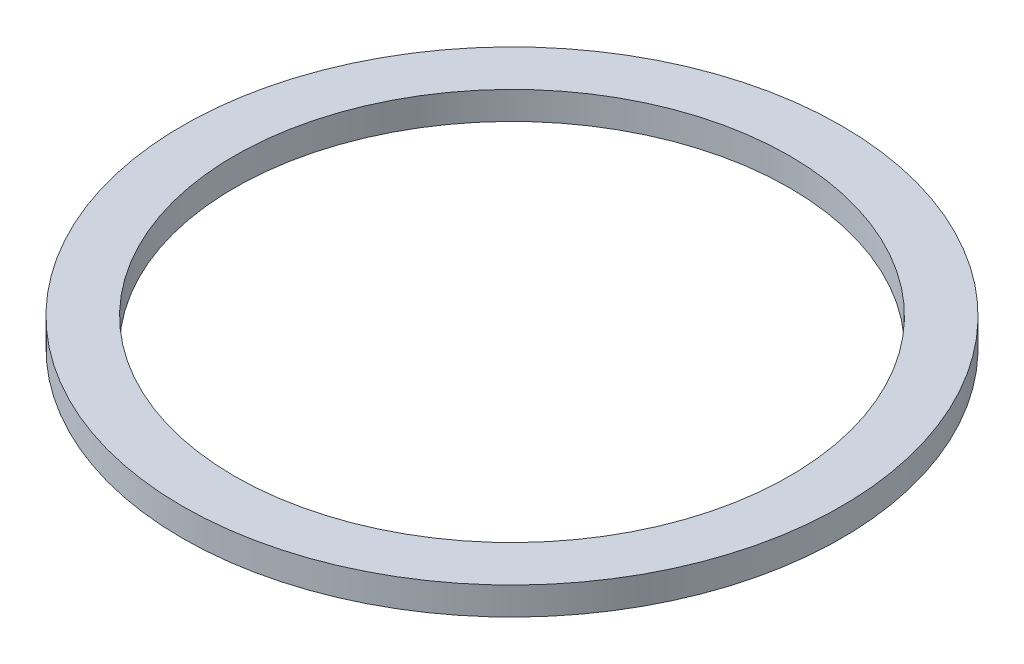
SolidWorks part; units mm, degrees
ref_plane "Front Plane" through (0, 0, 0) normal (0, 0, 1) x (1, 0, 0)
ref_plane "Top Plane" through (0, 0, 0) normal (0, 1, 0) x (1, 0, 0)
ref_plane "Right Plane" through (0, 0, 0) normal (1, 0, 0) x (0, 0, -1)
sketch "Sketch1" plane through (0, 0, 0) normal (0, 1, 0) x (1, 0, 0)
  circle A0 centre (0, 0) radius 47.5
  dimension "FLANGE_OD" = 95
extrude "Boss-Extrude1" add sketch "Sketch1" along normal blind 4
sketch "Sketch2" plane through (0, 0, 0) normal (0, 1, 0) x (1, 0, 0)
  circle A0 centre (0, 0) radius 40
  dimension "BORE_D" = 80
extrude "Cut-Extrude1" cut sketch "Sketch2" along normal through all
sketch "Sketch3" plane through (0, 4, 0) normal (0, 1, 0) x (1, 0, 0)
  circle A0 centre (0, 0) radius 21.7427 construction
  circle A1 centre (-21.7427, 0) radius 1.5
  dimension "BOLT_D" = 3
  dimension "BOLT_PCD" = 43.4854
extrude "Cut-Extrude2" cut sketch "Sketch3" against normal blind 3.4328 rebuild error yes
pattern_circular "CirPattern1" count 5 over 360 rebuild error yes
